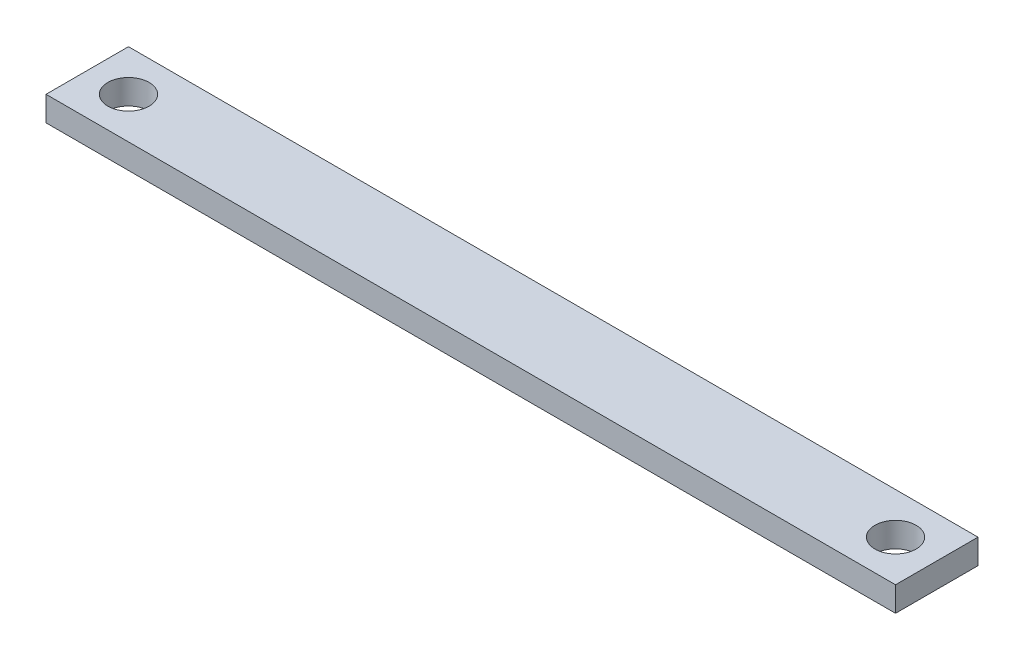
SolidWorks part; units mm, degrees
ref_plane "Front Plane" through (0, 0, 0) normal (0, 0, 1) x (1, 0, 0)
ref_plane "Top Plane" through (0, 0, 0) normal (0, 1, 0) x (1, 0, 0)
ref_plane "Right Plane" through (0, 0, 0) normal (1, 0, 0) x (0, 0, -1)
sketch "Sketch2" plane through (0, 0, 0) normal (0, 1, 0) x (1, 0, 0)
  line L1 (-51.5, -5) -> (51.5, -5)
  line L2 (-51.5, -5) -> (-51.5, 5)
  line L3 (-51.5, 5) -> (51.5, 5)
  line L4 (51.5, -5) -> (51.5, 5)
  line L5 (-51.5, -5) -> (51.5, 5) construction
  line L6 (-51.5, 5) -> (51.5, -5) construction
  point P0 (0, 0)
  dimension "D1" = 103
  dimension "D2" = 10
extrude "Boss-Extrude1" add sketch "Sketch2" along normal blind 3
sketch "Sketch3" plane through (0, 3, 0) normal (0, 1, 0) x (1, 0, 0)
  line L0 (-64.0944, 0) -> (61.2196, 0) construction
  line L1 (0, 21.5935) -> (0, -26.8203) construction
  circle A0 centre (-46.5, 0) radius 2.5
  circle A1 centre (46.5, 0) radius 2.5
  dimension "D1" = 5
  dimension "D2" = 46.5
extrude "Cut-Extrude1" cut sketch "Sketch3" against normal up to surface (3 mm away) up to face at (0, 0, 0)
